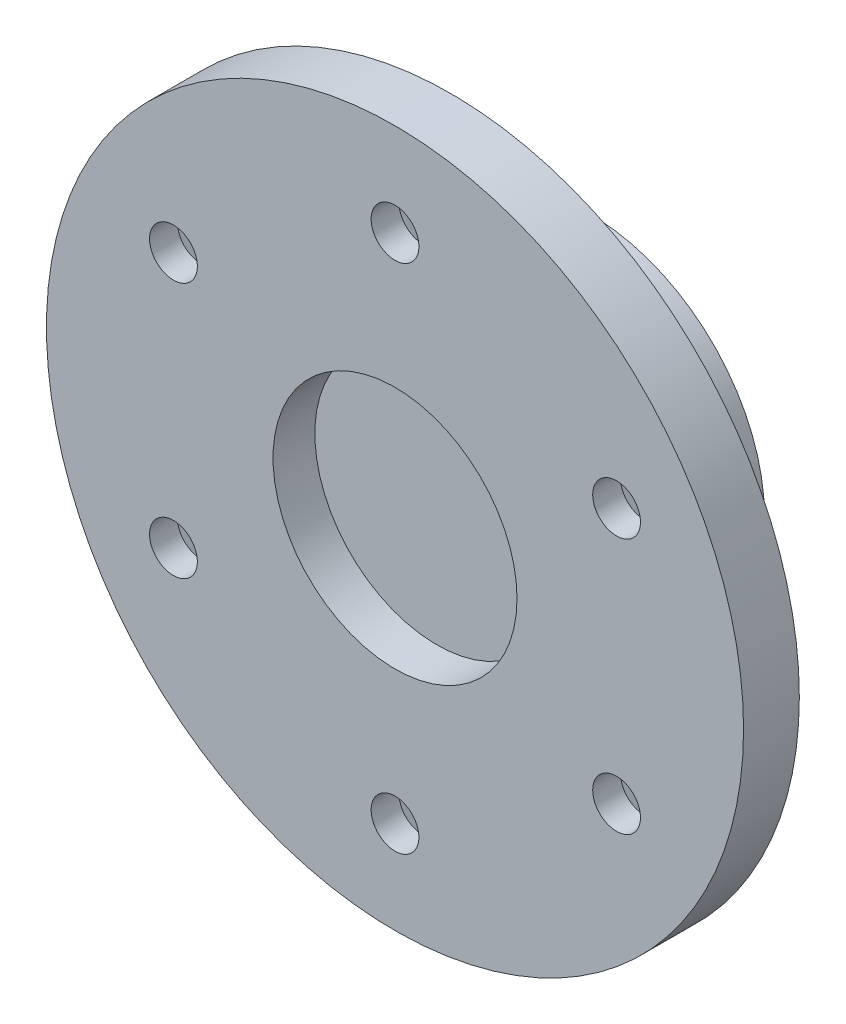
SolidWorks part; units mm, degrees
ref_plane "Front Plane" through (0, 0, 0) normal (0, 0, 1) x (1, 0, 0)
ref_plane "Top Plane" through (0, 0, 0) normal (0, 1, 0) x (1, 0, 0)
ref_plane "Right Plane" through (0, 0, 0) normal (1, 0, 0) x (0, 0, -1)
sketch "Sketch1" plane through (0, 0, 0) normal (0, 0, 1) x (1, 0, 0)
  circle A0 centre (0, 0) radius 25
  dimension "D1" = 50
extrude "Boss-Extrude1" add sketch "Sketch1" along normal blind 4
sketch "Sketch2" plane through (0, 0, 0) normal (0, 0, -1) x (-1, 0, 0)
  line L0 (0, 0) -> (0, 18.35) construction
  circle A0 centre (0, 18.35) radius 1.7136
  circle A1 centre (15.8916, 9.175) radius 1.7136
  circle A2 centre (15.8916, -9.175) radius 1.7136
  circle A3 centre (0, -18.35) radius 1.7136
  circle A4 centre (-15.8916, -9.175) radius 1.7136
  circle A5 centre (-15.8916, 9.175) radius 1.7136
  point P17 (0, 0)
  dimension "D1" = 18.35
  dimension "D2" = 6
extrude "Cut-Extrude1" cut sketch "Sketch2" against normal blind 4
sketch "Sketch3" plane through (0, 0, 0) normal (0, 0, -1) x (-1, 0, 0)
  line L0 (13.7265, 5.425) -> (18.0566, 5.425)
  line L1 (4.3301, 18.35) -> (2.1651, 22.1)
  line L2 (2.1651, 22.1) -> (-2.1651, 22.1)
  line L3 (-2.1651, 22.1) -> (-4.3301, 18.35)
  line L4 (-4.3301, 18.35) -> (-2.1651, 14.6)
  line L5 (-2.1651, 14.6) -> (2.1651, 14.6)
  line L6 (2.1651, 14.6) -> (4.3301, 18.35)
  line L7 (18.0566, 5.425) -> (20.2217, 9.175)
  line L8 (20.2217, 9.175) -> (18.0566, 12.925)
  line L9 (18.0566, 12.925) -> (13.7265, 12.925)
  line L10 (13.7265, 12.925) -> (11.5614, 9.175)
  line L11 (11.5614, 9.175) -> (13.7265, 5.425)
  line L12 (11.5614, -9.175) -> (13.7265, -12.925)
  line L13 (13.7265, -12.925) -> (18.0566, -12.925)
  line L14 (18.0566, -12.925) -> (20.2217, -9.175)
  line L15 (20.2217, -9.175) -> (18.0566, -5.425)
  line L16 (18.0566, -5.425) -> (13.7265, -5.425)
  line L17 (13.7265, -5.425) -> (11.5614, -9.175)
  line L18 (-2.1651, -14.6) -> (-4.3301, -18.35)
  line L19 (-4.3301, -18.35) -> (-2.1651, -22.1)
  line L20 (-2.1651, -22.1) -> (2.1651, -22.1)
  line L21 (2.1651, -22.1) -> (4.3301, -18.35)
  line L22 (4.3301, -18.35) -> (2.1651, -14.6)
  line L23 (2.1651, -14.6) -> (-2.1651, -14.6)
  line L24 (-13.7265, -5.425) -> (-18.0566, -5.425)
  line L25 (-18.0566, -5.425) -> (-20.2217, -9.175)
  line L26 (-20.2217, -9.175) -> (-18.0566, -12.925)
  line L27 (-18.0566, -12.925) -> (-13.7265, -12.925)
  line L28 (-13.7265, -12.925) -> (-11.5614, -9.175)
  line L29 (-11.5614, -9.175) -> (-13.7265, -5.425)
  line L30 (-11.5614, 9.175) -> (-13.7265, 12.925)
  line L31 (-13.7265, 12.925) -> (-18.0566, 12.925)
  line L32 (-18.0566, 12.925) -> (-20.2217, 9.175)
  line L33 (-20.2217, 9.175) -> (-18.0566, 5.425)
  line L34 (-18.0566, 5.425) -> (-13.7265, 5.425)
  line L35 (-13.7265, 5.425) -> (-11.5614, 9.175)
  circle A0 centre (0, 18.35) radius 3.75 construction
  point P42 (0, 0)
  dimension "D1" = 7.5
  dimension "D2" = 6
extrude "Cut-Extrude2" cut sketch "Sketch3" against normal blind 2
sketch "Sketch4" plane through (0, 0, 0) normal (0, 0, -1) x (-1, 0, 0)
  line L0 (0, 0) -> (0, 0.5) construction
  circle A1 centre (0, 0.5) radius 2.5
  circle A2 centre (0, 0) radius 12.5
  dimension "D1" = 5
  dimension "D3" = 25
  dimension "D2" = 0.5
extrude "Boss-Extrude2" add sketch "Sketch4" along normal blind 10
ref_plane "Plane1" through (0, 12.5, 0) normal (0, 1, 0) x (1, 0, 0)
sketch "Sketch5" plane through (0, 12.5, 0) normal (0, 1, 0) x (1, 0, 0)
  circle A0 centre (0, 5) radius 1.6
  dimension "D1" = 3.2
  dimension "D2" = 5
  dimension "D3" = 12.5
extrude "Cut-Extrude3" cut sketch "Sketch5" against normal blind 12.5
sketch "Sketch6" plane through (0, 12.5, 0) normal (0, 1, 0) x (1, 0, 0)
  circle A0 centre (0, 5) radius 3.1
  dimension "D1" = 6.2
extrude "Cut-Extrude4" cut sketch "Sketch6" against normal blind 6
ref_plane "Plane2" through (0, 1.5, 0) normal (0, 1, 0) x (1, 0, 0)
fillet "Fillet1" radius 1.5 1 edges at (12.5, 0, 0) type face fillet first side face at (0.608, 12.4852, -8.0398) second side face at (12.5, 0, 0)
sketch "Sketch9" plane through (0, 0, 4) normal (0, 0, 1) x (1, 0, 0)
  circle A0 centre (0, 0) radius 8.75
  dimension "D1" = 17.5
extrude "Cut-Extrude6" cut sketch "Sketch9" against normal blind 3
sketch "Sketch12" plane through (0, 0, -10) normal (0, 0, -1) x (-1, 0, 0)
  line L2 (1.0981, -4.0981) -> (4.0981, 1.0981)
  line L3 (4.0981, 1.0981) -> (6.4796, -0.2769)
  line L4 (6.4796, -0.2769) -> (3.4796, -5.4731)
  line L5 (3.4796, -5.4731) -> (1.0981, -4.0981)
  line L6 (-2.75, 4.5) -> (2.75, 4.5)
  line L7 (-2.75, 4.5) -> (-2.75, 2)
  line L8 (-2.75, 2) -> (2.75, 2)
  line L9 (2.75, 4.5) -> (2.75, 2)
  line L10 (0, 0.5) -> (0, -6.5) construction
  line L11 (-3.4796, -5.4731) -> (-1.0981, -4.0981)
  line L12 (-6.4796, -0.2769) -> (-3.4796, -5.4731)
  line L13 (-4.0981, 1.0981) -> (-6.4796, -0.2769)
  line L14 (-1.0981, -4.0981) -> (-4.0981, 1.0981)
  circle A0 centre (0, 0) radius 12.5 construction
  point P1 (0, 2)
  point P2 (2.5981, -1.5)
  dimension "D1" = 5.5
  dimension "D2" = 2
  dimension "D3" = 3
  dimension "D4" = 2.5
  dimension "D5" = 6
  dimension "D6" = 2.75
extrude "Cut-Extrude7" cut sketch "Sketch12" against normal blind 10
ref_plane "Plane3" through (-6.4796, -0.2769, -10) normal (-0.5, 0.866, 0) x (0.866, 0.5, 0)
sketch "Sketch16" plane through (0, 0, -10) normal (0, 0, -1) x (-1, 0, 0)
  line L0 (-2.5981, -1.5) -> (-10.8253, -6.25)
  line L1 (-1.0981, -4.0981) -> (-4.0981, 1.0981) construction
  line L2 (-2.5981, -1.5) -> (-1.9158, -1.1061)
  circle A0 centre (0, 0) radius 12.5 construction
  arc A1 (-2, 2) -> (2, 2) centre (0, 0.5) ccw construction
sketch "Sketch17" plane through (2.5981, -1.5, 0) normal (0.866, -0.5, 0) x (0, 0, -1)
  line L0 (10, 0) -> (5, 0)
  line L1 (10, -3) -> (10, 3) construction
  circle A0 centre (5, 0) radius 1.6
  dimension "D3" = 3.2
  dimension "D1" = 5
  dimension "D2" = 0
  dimension "D4" = 0
extrude "Cut-Extrude8" cut sketch "Sketch17" along normal blind 10 and the other way blind 2 contours A0 region at (2.5981, -1.5, -3.4453)
sketch "Sketch18" plane through (-2.5981, -1.5, 0) normal (-0.866, -0.5, 0) x (0, 0, 1)
  line L0 (-10, 0) -> (-5, 0)
  line L1 (-10, 3) -> (-10, -3) construction
  circle A0 centre (-5, 0) radius 1.6
  dimension "D3" = 3.2
  dimension "D1" = 5
  dimension "D2" = 0
extrude "Cut-Extrude9" cut sketch "Sketch18" against normal blind 2 and the other way blind 30 contours A0 region at (-1.8207, -2.8464, -5)
sketch "Sketch20" plane through (-4.9796, -2.875, 0) normal (0.866, 0.5, 0) x (0, 0, -1)
  circle A0 centre (5, 0) radius 3.1
  dimension "D1" = 6.2
extrude "Cut-Extrude10" cut sketch "Sketch20" against normal blind 4 from offset 3 offset against normal yes
sketch "Sketch21" plane through (4.9796, -2.875, 0) normal (-0.866, 0.5, 0) x (0, 0, 1)
  circle A0 centre (-5, 0) radius 3.1
  dimension "D1" = 6.2
extrude "Cut-Extrude11" cut sketch "Sketch21" against normal blind 4 from offset 3 offset against normal yes
equation "\"mm\"=1.5"
